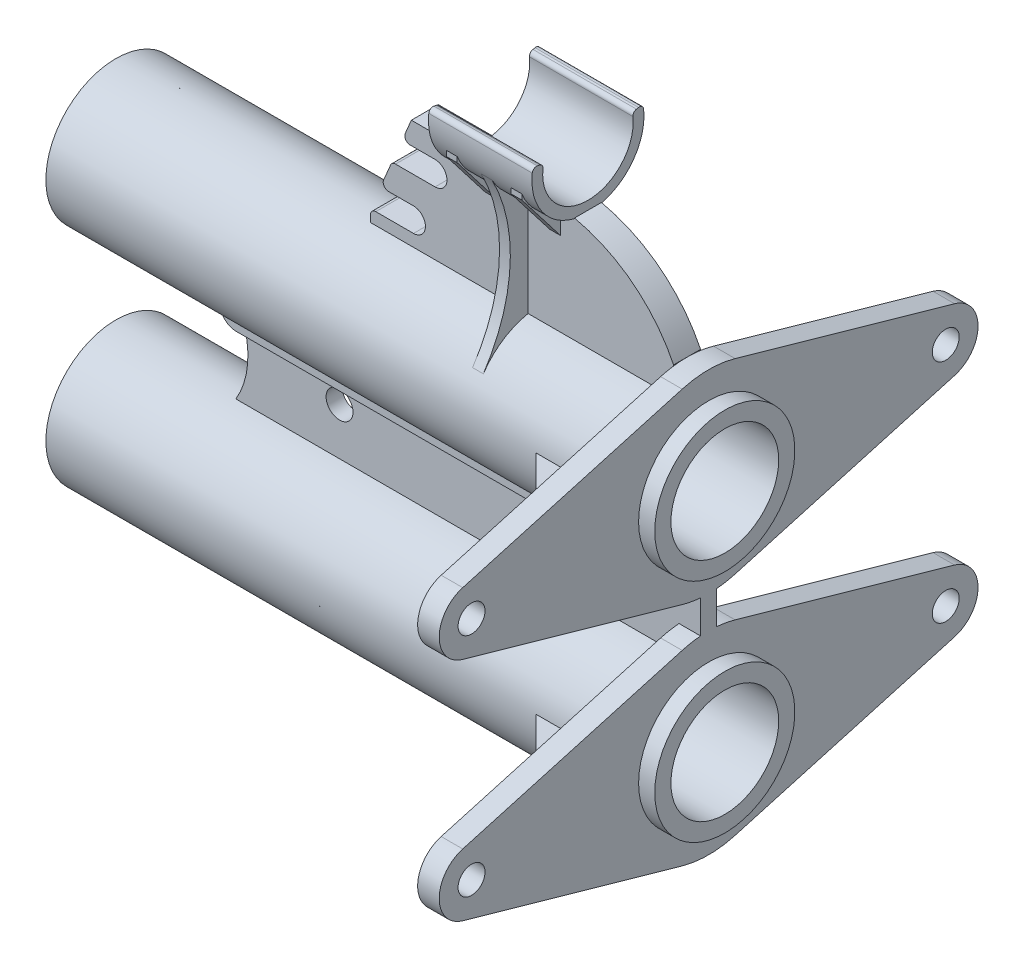
SolidWorks part; units mm, degrees
ref_plane "Front" through (0, 0, 0) normal (0, 0, 1) x (1, 0, 0)
ref_plane "Top" through (0, 0, 0) normal (0, 1, 0) x (1, 0, 0)
ref_plane "Right" through (0, 0, 0) normal (1, 0, 0) x (0, 0, -1)
sketch "Sketch1" plane through (0, 0, 0) normal (1, 0, 0) x (0, 0, -1)
  circle A0 centre (0, 0) radius 8.255
  dimension "D1" = 16.51
extrude "tube" add sketch "Sketch1" against normal blind 69.85
sketch "Sketch2" plane through (0, 0, 0) normal (1, 0, 0) x (0, 0, -1)
  line L0 (27.94, 0) -> (-27.94, 0) construction
  line L1 (-28.9791, 3.6656) -> (-3.1173, 10.9967)
  line L2 (3.1173, 10.9967) -> (28.9791, 3.6656)
  line L3 (28.9791, -3.6656) -> (3.1173, -10.9967)
  line L4 (-28.9791, -3.6656) -> (-3.1173, -10.9967)
  arc A0 (-28.9791, 3.6656) -> (-28.9791, -3.6656) centre (-27.94, 0) ccw
  circle A1 centre (0, 0) radius 11.43
  arc A2 (-3.1173, -10.9967) -> (3.1173, -10.9967) centre (0, 0) ccw
  arc A3 (28.9791, -3.6656) -> (28.9791, 3.6656) centre (27.94, 0) ccw
  arc A4 (3.1173, 10.9967) -> (-3.1173, 10.9967) centre (0, 0) ccw
  circle A5 centre (-27.94, 0) radius 1.5875
  circle A6 centre (27.94, 0) radius 1.5875
  dimension "D2" = 7.62
  dimension "D4" = 3.175
  dimension "D3" = 63.5
  dimension "D1" = 3.175
extrude "flange" add sketch "Sketch2" against normal blind 2.54
sketch "Sketch3" plane through (-69.85, 0, 0) normal (-1, 0, 0) x (0, 0, 1)
  circle A1 centre (0, 0) radius 6.35
  circle A2 centre (0, 0) radius 6.35
  dimension "D1" = 1.905
extrude "hole" cut sketch "Sketch3" against normal through all
sketch "Sketch4" plane through (0, 0, 0) normal (1, 0, 0) x (0, 0, -1)
  circle A0 centre (0, 0) radius 6.35 construction
  circle A1 centre (0, 0) radius 8.255
  circle A2 centre (0, 0) radius 8.255
  circle A3 centre (0, 0) radius 6.35
  dimension "D1" = 1.905
extrude "circular boss" add sketch "Sketch4" along normal blind 1.905
sketch "Sketch6" plane through (0, 0, 0) normal (0, 1, 0) x (1, 0, 0)
  line L0 (-2.54, 7.3025) -> (-13.0175, 7.3025)
  line L1 (-2.54, 7.3025) -> (-2.54, 17.78)
  line L2 (-2.54, 8.255) -> (-69.85, 8.255) construction
  line L4 (-2.54, 3.1173) -> (-2.54, 28.9791) construction
  line L5 (-13.0175, 7.3025) -> (-2.54, 17.78)
  point P7 (-12.065, 8.255)
  dimension "D1" = 0.9525
  dimension "D2" = 9.525
  dimension "D3" = 9.525
extrude "brace" add sketch "Sketch6" along normal mid plane 1.905
mirror "Mirror1" about plane through (0, 0, 0) normal (0, 0, 1) of "brace"
sketch "Sketch5" plane through (0, 0, 0) normal (0, 0, 1) x (1, 0, 0)
  line L0 (0, 7.3025) -> (-55.372, 7.3025)
  line L1 (0, 7.3025) -> (0, 19.3675)
  line L2 (-55.372, 19.3675) -> (0, 19.3675)
  line L3 (-2.54, 8.255) -> (-69.85, 8.255) construction
  line L4 (0, 3.6656) -> (0, 10.9967) construction
  line L5 (-2.54, 8.255) -> (-69.85, 8.255) construction
  line L6 (-63.3105, 18.415) -> (7.5357, 18.415) construction
  arc A0 (-55.372, 7.3025) -> (-55.372, 19.3675) centre (-63.3105, 13.335) ccw
  circle A1 centre (-42.545, 13.7414) radius 1.5875
  circle A2 centre (-12.7, 13.7414) radius 1.5875
  dimension "D6" = 3.175
  dimension "D1" = 0.9525
  dimension "D2" = 53.34
  dimension "D3" = 55.372
  dimension "D4" = 0.9525
  dimension "D5" = 10.16
  dimension "D7" = 12.7
  dimension "D8" = 29.845
  dimension "D9" = 5.4864
extrude "center plate" add sketch "Sketch5" along normal mid plane 1.905
pattern_linear "upper tube&flange" count 2 spacing 26.67 along (0, 1, 0) of "Mirror1", "brace", "tube", "flange", "hole", "circular boss"
sketch "Sketch7" plane through (0, 0, 0) normal (0, 0, 1) x (1, 0, 0)
  line L0 (-33.4455, 47.625) -> (-17.78, 47.625)
  line L1 (-2.54, 34.925) -> (-69.85, 34.925) construction
  line L2 (-2.54, 30.3356) -> (-2.54, 37.6667) construction
  line L3 (-2.54, 33.9725) -> (-2.54, 38.1)
  line L4 (-38.2715, 33.9725) -> (-38.2715, 36.195)
  line L5 (0, 38.1) -> (-2.54, 38.1) construction
  line L6 (-2.54, 33.9725) -> (-69.85, 33.9725)
  line L7 (-2.54, 33.9725) -> (-38.2715, 33.9725)
  line L9 (-38.2715, 36.195) -> (-33.1915, 36.195)
  line L11 (-33.1915, 39.0029) -> (-37.086, 39.0029)
  line L12 (-35.7315, 42.2108) -> (-30.6515, 42.2108)
  line L14 (-30.6515, 45.0187) -> (-34.546, 45.0187)
  line L15 (-34.546, 45.0187) -> (-33.4455, 47.625)
  line L16 (-35.7315, 42.2108) -> (-37.086, 39.0029)
  arc A0 (-2.54, 38.1) -> (-17.78, 47.625) centre (-17.78, 30.6705) ccw
  arc A1 (-33.1915, 39.0029) -> (-33.1915, 36.195) centre (-33.1915, 37.5989) cw
  arc A2 (-30.6515, 42.2108) -> (-30.6515, 45.0187) centre (-30.6515, 43.6147) ccw
  dimension "D3" = 5.08
  dimension "D1" = 12.7
  dimension "D2" = 15.24
  dimension "D5" = 7.62
  dimension "D6" = 1.27
  dimension "D7" = 30.9055
  dimension "D8" = 35.7315
  dimension "D9" = 2.6063
  dimension "D4" = 0.9525
extrude "sight" add sketch "Sketch7" along normal mid plane 3.175
fillet "R025" radius 0.635 4 edges at (-37.086, 39.0029, 0) (-35.7315, 42.2108, 0) (-34.546, 45.0187, 0) (-38.2715, 36.195, 0)
ref_plane "centersupport" through (-20.32, 0, 0) normal (1, 0, 0) x (0, 0, -1)
sketch "Sketch8" plane through (-20.32, 0, 0) normal (1, 0, 0) x (0, 0, -1)
  line L0 (-10.4652, 54.864) -> (5.9346, 54.864) construction
  line L1 (-1.5875, 47.625) -> (1.5875, 47.625) construction
  arc A0 (-6.4807, 54.864) -> (6.4807, 54.864) centre (0, 53.594) ccw
  dimension "D1" = 13.208
  dimension "D2" = 1.27
  dimension "D3" = 0.635
extrude "ammo holder" add sketch "Sketch8" along normal mid plane 12.192 thin thin type one direction reverse wall 1.27
fillet "R020" radius 0.508 4 edges at (-20.32, 54.864, 6.4807) (-20.32, 54.6198, 5.2344) (-20.32, 54.6198, -5.2344) (-20.32, 54.864, -6.4807)
sketch "Sketch9" plane through (-20.32, 0, 0) normal (1, 0, 0) x (0, 0, -1)
  line L0 (1.5875, 38.1) -> (1.5875, 47.2479) construction
  line L1 (0, 50) -> (0, -50) construction
  line L3 (1.5875, 34.7709) -> (1.5875, 47.1836)
  arc A0 (6.8644, 31.2553) -> (1.5875, 34.7709) centre (0, 26.67) ccw
  arc A1 (5.8472, 50.5244) -> (6.8644, 31.2553) centre (22.5693, 41.7457) ccw
  arc A2 (1.5875, 47.1836) -> (6.564, 54.3195) centre (0, 53.594) ccw construction
  circle A3 centre (0, 26.67) radius 8.255 construction
  arc A4 (1.5875, 47.1836) -> (5.8472, 50.5244) centre (0, 53.594) ccw
  dimension "D1" = 3.683
extrude "support" add sketch "Sketch9" against normal mid plane 1.27
ref_plane "brace plane" through (-23.495, 0, 0) normal (-1, 0, 0) x (0, 0, 1)
sketch "Sketch10" plane through (-23.495, 0, 0) normal (-1, 0, 0) x (0, 0, 1)
  line L0 (-1.5875, 44.6436) -> (-6.1428, 50.5345)
  line L2 (-6.1428, 50.5345) -> (-6.1428, 51.1695)
  line L3 (-1.5875, 34.7709) -> (-1.5875, 47.1836) construction
  line L4 (-1.5875, 44.6436) -> (-1.5875, 47.1836)
  line L5 (-1.5875, 47.2479) -> (-1.5875, 38.1) construction
  arc A0 (-6.1428, 51.1695) -> (-1.5875, 47.1836) centre (0, 53.594) ccw
  arc A1 (-6.564, 54.3195) -> (-1.5875, 47.1836) centre (0, 53.594) ccw construction
  arc A2 (-6.6903, 54.3335) -> (-1.618, 47.0604) centre (0, 53.594) ccw
  arc A3 (-6.6903, 54.3335) -> (-0.1539, 46.8648) centre (0, 53.594) ccw construction
  dimension "D1" = 2.54
  dimension "D3" = 0.635
  dimension "D2" = 0.127
extrude "support brace" add sketch "Sketch10" along normal blind 1.27
mirror "Mirror2" about plane through (-20.32, 0, 0) normal (1, 0, 0) of "support brace"
sketch "Sketch11" plane through (-2.54, 0, 0) normal (-1, 0, 0) x (0, 0, 1)
  line L0 (-0.9525, 15.2798) -> (-0.9525, 18.4701) construction
  line L1 (-0.9525, 17.0203) -> (-0.9525, 18.4701)
  line L4 (-2.8575, 17.0203) -> (-0.9525, 17.0203)
  line L5 (-2.8575, 17.0203) -> (-2.8575, 18.9253)
  arc A0 (-8.1999, 25.7175) -> (-0.9525, 18.4701) centre (0, 26.67) ccw construction
  arc A1 (-2.8575, 18.9253) -> (-0.9525, 18.4701) centre (0, 26.67) ccw
  dimension "D1" = 1.905
  dimension "D2" = 1.905
extrude "rail" add sketch "Sketch11" along normal up to surface (51.5061 mm away) up to face at (-54.052, 13.335, -0.4762)
fillet "R075" radius 1.905 1 edges at (-54.0461, 17.0203, -1.905)
mirror "Mirror3" about plane through (0, 0, 0) normal (0, 0, 1) of "R075", "rail", "support", "support brace", "Mirror2"
